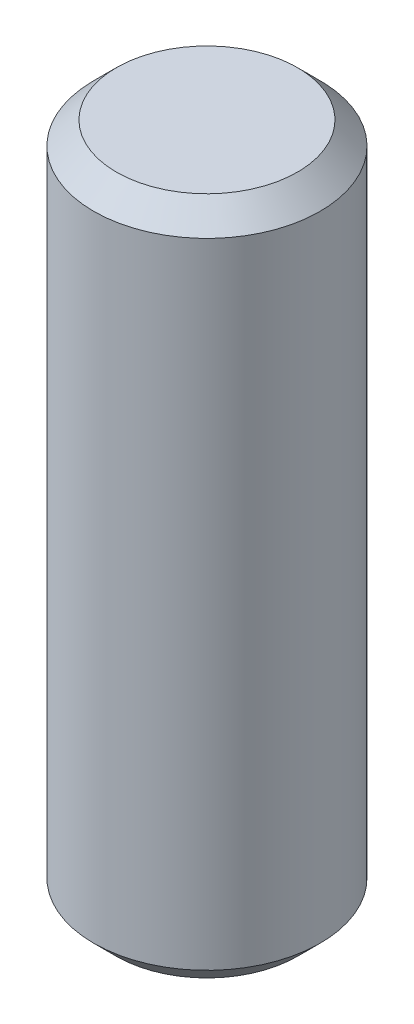
SolidWorks part; units mm, degrees
ref_plane "Front Plane" through (0, 0, 0) normal (0, 0, 1) x (1, 0, 0)
ref_plane "Top Plane" through (0, 0, 0) normal (0, 1, 0) x (1, 0, 0)
ref_plane "Right Plane" through (0, 0, 0) normal (1, 0, 0) x (0, 0, -1)
sketch "Sketch1" plane through (0, 0, 0) normal (0, 1, 0) x (1, 0, 0)
  circle A0 centre (0, 0) radius 2
  dimension "D1" = 4
extrude "Boss-Extrude1" add sketch "Sketch1" along normal blind 12
chamfer "Chamfer1" distance 0.4 angle 45 2 edges at (0, 0, 2) (0, 12, 2)
